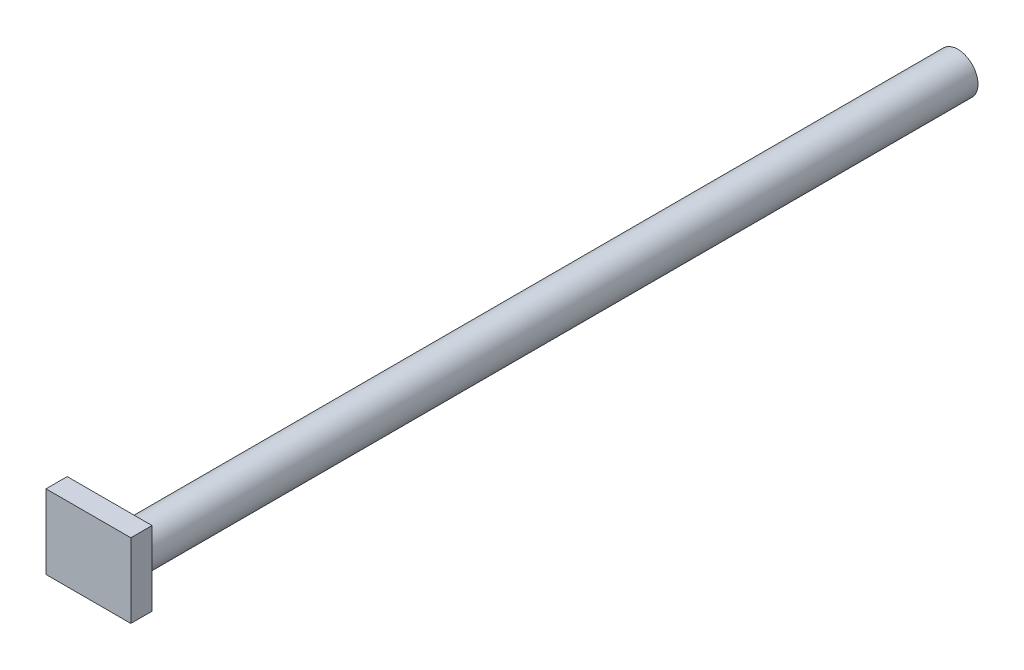
SolidWorks part; units mm, degrees
ref_plane "Front Plane" through (0, 0, 0) normal (0, 0, 1) x (1, 0, 0)
ref_plane "Top Plane" through (0, 0, 0) normal (0, 1, 0) x (1, 0, 0)
ref_plane "Right Plane" through (0, 0, 0) normal (1, 0, 0) x (0, 0, -1)
sketch "Sketch1" plane through (0, 0, 0) normal (0, 0, 1) x (1, 0, 0)
  circle A0 centre (0, 0) radius 9.525
  dimension "D1" = 19.05
extrude "Boss-Extrude1" add sketch "Sketch1" along normal blind 400
sketch "Sketch2" plane through (0, 0, 400) normal (0, 0, 1) x (1, 0, 0)
  line L0 (0, 0) -> (0, 25) construction
  line L1 (20, -10) -> (-20, -10)
  line L2 (20, -10) -> (20, 25)
  line L3 (20, 25) -> (-20, 25)
  line L4 (-20, -10) -> (-20, 25)
  point P0 (0, 0)
  dimension "D1" = 40
  dimension "D2" = 10
extrude "Boss-Extrude2" add sketch "Sketch2" along normal blind 10
